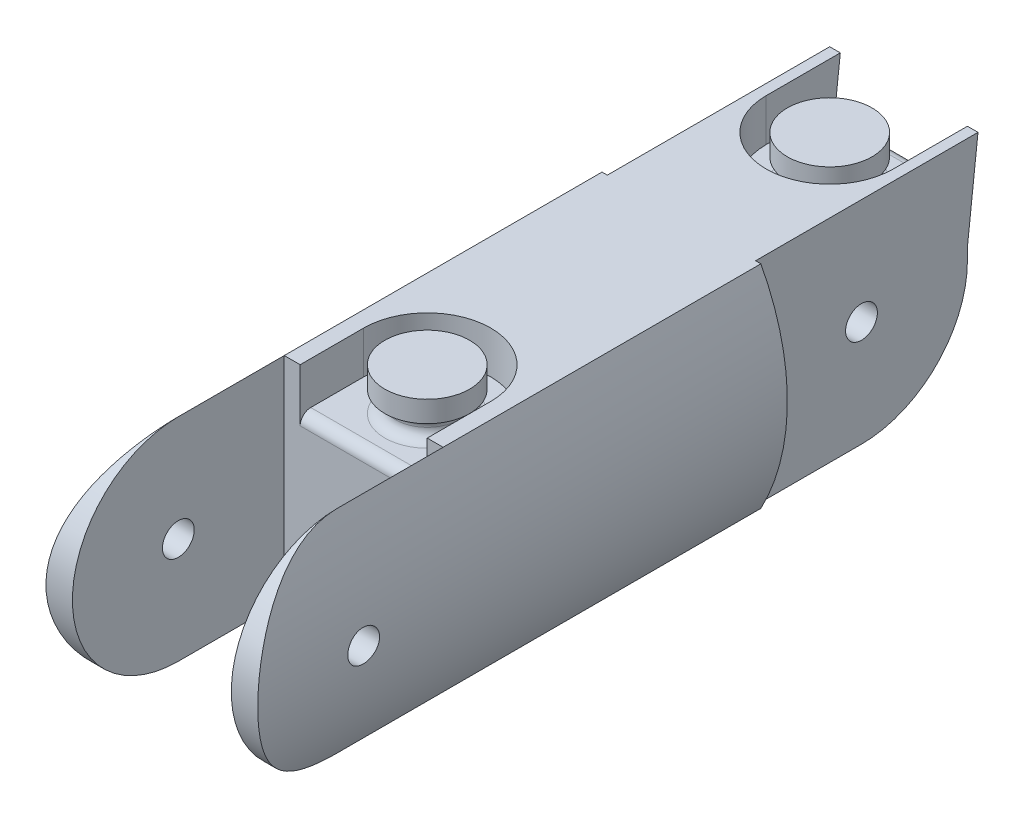
SolidWorks part; units mm, degrees
ref_plane "Alzado" through (0, 0, 0) normal (0, 0, 1) x (1, 0, 0)
ref_plane "Planta" through (0, 0, 0) normal (0, 1, 0) x (1, 0, 0)
ref_plane "Vista lateral" through (0, 0, 0) normal (1, 0, 0) x (0, 0, -1)
sketch "Croquis2" plane through (0, 0, 0) normal (0, 0, 1) x (1, 0, 0)
  line L5 (-7.5, -10) -> (7.5, -10)
  line L7 (-7.5, 10) -> (7.5, 10)
  line L9 (-7.5, -10) -> (7.5, 10) construction
  line L10 (-7.5, 10) -> (7.5, -10) construction
  arc A2 (-7.5, 10) -> (-7.5, -10) centre (11.25, 0) ccw
  arc A3 (7.5, -10) -> (7.5, 10) centre (-11.25, 0) ccw
  point P0 (0, 0)
  dimension "D1" = 15
  dimension "D2" = 20
extrude "Saliente-Extruir2" add sketch "Croquis2" along normal blind 50
sketch "Croquis4" plane through (0, 0, 0) normal (0, 0, -1) x (-1, 0, 0)
  line L1 (7.5, -10) -> (-7.5, -10) construction
  circle A0 centre (0, -7) radius 1.5
  dimension "D2" = 3
  dimension "D1" = 3
extrude "Cortar-Extruir1" cut sketch "Croquis4" against normal blind 50
sketch "Croquis3" plane through (0, 0, 0) normal (0, 0, -1) x (-1, 0, 0)
  line L8 (7.5, -10) -> (-7.5, -10) construction
  line L10 (7, 10) -> (7, -10)
  line L11 (7, -10) -> (3, -10)
  line L12 (-7, 10) -> (-7, -10)
  line L13 (7, 10) -> (-7, -10) construction
  line L14 (7, -10) -> (-7, 10) construction
  line L17 (-3, -10) -> (-7, -10)
  line L19 (-3, -3) -> (3, -3)
  line L20 (-3, -3) -> (-3, -10)
  line L21 (3, -3) -> (3, -10)
  line L22 (-7, 10) -> (7, 10)
  point P0 (0, 0)
  dimension "D1" = 14
  dimension "D2" = 4
  dimension "D3" = 4
  dimension "D4" = 7
extrude "Saliente-Extruir3" add sketch "Croquis3" along normal blind 20
sketch "Croquis8" plane through (-7, 0, 0) normal (-1, 0, 0) x (0, 0, 1)
  line L0 (-20, -10) -> (-20, 10) construction
  line L1 (-20, -10) -> (0, -10) construction
  circle A0 centre (-10, 0) radius 1.5
  point P4 (-20, 0)
  dimension "D1" = 3
  dimension "D2" = 10
  dimension "D3" = 10
extrude "Cortar-Extruir4" cut sketch "Croquis8" against normal blind 14
fillet "Redondeo1" radius 10 2 edges at (-5, -10, -20) (5, -10, -20)
sketch "Croquis6" plane through (0, 0, 50) normal (0, 0, 1) x (1, 0, 0)
  line L1 (-7.5, 10) -> (7.5, 10)
  line L2 (-7.5, 10) -> (-7.5, -10)
  line L3 (-7.5, -10) -> (7.5, -10)
  line L4 (7.5, 10) -> (7.5, -10)
extrude "Cortar-Extruir2" cut sketch "Croquis6" against normal blind 20
sketch "Croquis7" plane through (0, 0, 0) normal (1, 0, 0) x (0, 0, -1)
  line L0 (-50, 10) -> (-50, -10) construction
  line L2 (-40, -10) -> (-55, -10)
  line L4 (-40, 10) -> (-55, 10)
  line L5 (-55, -10) -> (-55, 10)
  arc A0 (-40, 10) -> (-40, -10) centre (-40, 0) ccw
  circle A1 centre (-40, 0) radius 1.5
  dimension "D3" = 10
  dimension "D4" = 3
  dimension "D1" = 10
  dimension "D2" = 15
  dimension "D5" = 20
extrude "Cortar-Extruir3" cut sketch "Croquis7" against normal through all both and the other way through all
sketch "Sketch1" plane through (0, 10, 0) normal (0, 1, 0) x (1, 0, 0)
  line L0 (-7, 20) -> (7, 20) construction
  line L1 (7.5, -30) -> (-7.5, -30) construction
  line L4 (-6, -24) -> (-6, -30)
  line L5 (-6, -30) -> (6, -30)
  line L6 (6, -24) -> (6, -30)
  line L8 (-6, 14) -> (-6, 20)
  line L9 (-6, 20) -> (6, 20)
  line L10 (6, 14) -> (6, 20)
  arc A0 (6, -24) -> (-6, -24) centre (0, -24) ccw
  arc A1 (-6, 14) -> (6, 14) centre (0, 14) ccw
  dimension "D2" = 12
  dimension "D4" = 12
  dimension "D1" = 6
  dimension "D3" = 6
extrude "Cut-Extrude1" cut sketch "Sketch1" against normal blind 4
sketch "Sketch2" plane through (0, 6, 0) normal (0, 1, 0) x (1, 0, 0)
  circle A0 centre (0, -24) radius 3
  circle A1 centre (0, 14) radius 3
  dimension "D1" = 6
  dimension "D2" = 6
extrude "Boss-Extrude1" add sketch "Sketch2" along normal blind 2
sketch "Sketch3" plane through (0, 8, 0) normal (0, 1, 0) x (1, 0, 0)
  circle A0 centre (0, -24) radius 4
  circle A1 centre (0, 14) radius 4
  dimension "D1" = 8
  dimension "D2" = 8
extrude "Boss-Extrude2" add sketch "Sketch3" along normal blind 2
fillet "Fillet2" radius 1 4 edges at (0, 8, -11) (0, 6, -11) (0, 8, 27) (0, 6, 27)
fillet "Fillet3" radius 1 2 edges at (0, 6, -20) (0, 6, 30)
fillet "Fillet4" radius 1 2 edges at (-1.5, -7, 0) (1.5, -7, 30)
sketch "Sketch4" plane through (7, 0, 0) normal (1, 0, 0) x (0, 0, -1)
  line L0 (20, 10) -> (21, 10)
  line L1 (21, 10) -> (19.5394, -3)
  line L2 (19.5394, -3) -> (20, 10)
  dimension "D1" = 1
sketch "Sketch5" plane through (-7, 0, 0) normal (-1, 0, 0) x (0, 0, 1)
  line L0 (-20, 10) -> (-21, 10)
  line L1 (-21, 10) -> (-19.5394, -3)
  line L2 (-19.5394, -3) -> (-20, 10)
extrude "Boss-Extrude3" add sketch "Sketch4" against normal blind 1
extrude "Boss-Extrude4" add sketch "Sketch5" against normal blind 1
sketch "Sketch6" plane through (0, 0, 0) normal (0, 0, -1) x (-1, 0, 0)
  line L0 (-7, 10) -> (-7, -10) construction
  line L1 (-3, -2) -> (3, -2)
  line L2 (-3, -4) -> (3, -4)
  line L3 (3, -10) -> (-3, -10) construction
  arc A0 (-3, -2) -> (-3, -4) centre (-3, -3) ccw
  arc A1 (3, -4) -> (3, -2) centre (3, -3) ccw
  dimension "D1" = 2
  dimension "D2" = 2
  dimension "D3" = 6
  dimension "D4" = 4
  dimension "D5" = 8
extrude "Cut-Extrude2" cut sketch "Sketch6" along normal blind 50 from offset 28 offset against normal yes
sketch "Sketch7" plane through (0, -10, 0) normal (0, -1, 0) x (1, 0, 0)
  line L0 (7, -20) -> (-7, -20) construction
  line L1 (-4, 0) -> (4, 0)
  line L2 (-4, 0) -> (-4, -20)
  line L3 (-4, -20) -> (4, -20)
  line L4 (4, 0) -> (4, -20)
  line L5 (-7, -10) -> (-7, 0) construction
  dimension "D1" = 8
  dimension "D2" = 3
extrude "Cut-Extrude3" cut sketch "Sketch7" against normal blind 7
fillet "Fillet5" radius 0.5 3 edges at (3.7071, -3.7071, 0) (-3.7071, -3.7071, 0) (0, -4, 0)
